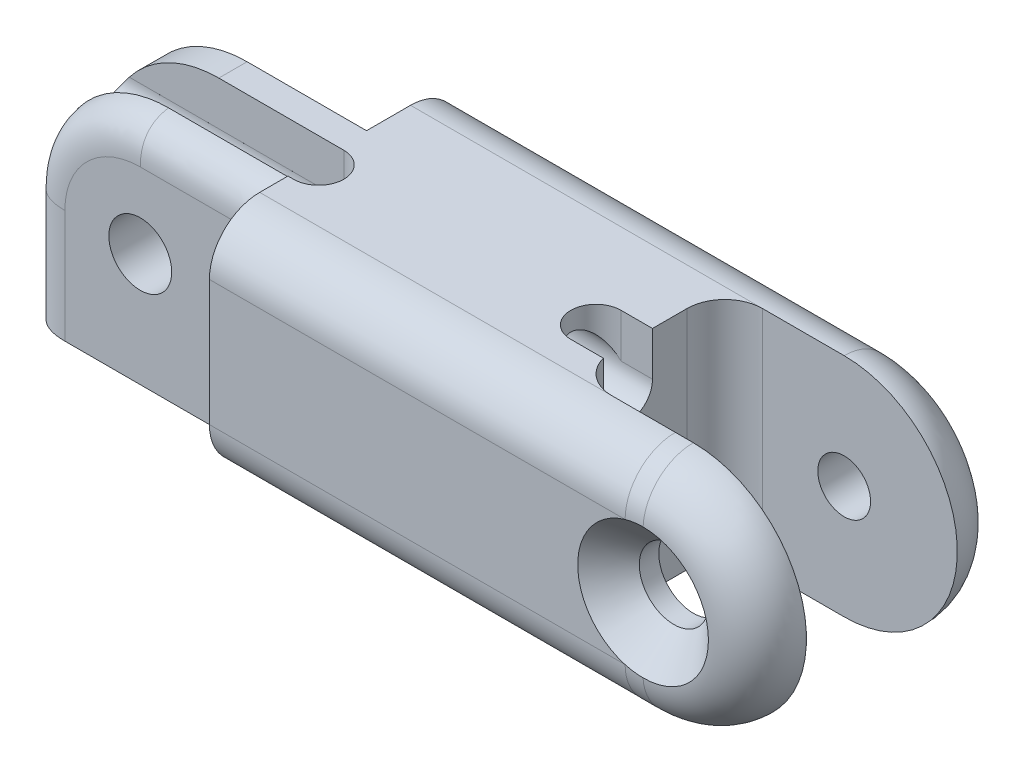
SolidWorks part; units mm, degrees
ref_plane "Front Plane" through (0, 0, 0) normal (0, 0, 1) x (1, 0, 0)
ref_plane "Top Plane" through (0, 0, 0) normal (0, 1, 0) x (1, 0, 0)
ref_plane "Right Plane" through (0, 0, 0) normal (1, 0, 0) x (0, 0, -1)
sketch "Sketch2" plane through (0, 0, 0) normal (0, 1, 0) x (1, 0, 0)
  line L0 (-12.5, 10) -> (31, 10)
  line L1 (31, 10) -> (31, 6)
  line L2 (31, 6) -> (15.5, 6)
  line L3 (12.5, 3) -> (12.5, -3)
  line L4 (15.5, -6) -> (31, -6)
  line L5 (31, -6) -> (31, -10)
  line L7 (-31, -6) -> (-31, 2.5)
  line L8 (-49.3622, 0) -> (56.3776, 0) construction
  line L9 (0, 21.2372) -> (0, -19.0689) construction
  line L10 (12.5, 3) -> (15.5, 3) construction
  line L11 (15.5, 3) -> (15.5, 6) construction
  line L16 (-12.5, -10) -> (31, -10)
  line L18 (-31, -6) -> (-12.5, -6)
  line L19 (-12.5, -6) -> (-12.5, -10)
  line L20 (-31, 2.5) -> (-12.5, 2.5)
  line L21 (-12.5, 2.5) -> (-12.5, 10)
  arc A0 (15.5, 6) -> (12.5, 3) centre (15.5, 3) ccw
  arc A1 (15.5, -6) -> (12.5, -3) centre (15.5, -3) cw
  point P13 (15.5, 3)
  dimension "D1" = 62
  dimension "D2" = 20
  dimension "D3" = 4
  dimension "D4" = 18.5
  dimension "D5" = 12
  dimension "D6" = 3
  dimension "D7" = 3
  dimension "D8" = 7.5
  dimension "D9" = 4
  dimension "D10" = 8.5
  dimension "D11" = 18.5
extrude "Boss-Extrude1" add sketch "Sketch2" along normal blind 18
sketch "Sketch5" plane through (0, 0, 10) normal (0, 0, 1) x (1, 0, 0)
  line L0 (-31, 9) -> (31.8491, 9) construction
  line L1 (-22, 18) -> (-22, 0) construction
  line L2 (31, 18) -> (31, 0) construction
  line L3 (-12.5, 18) -> (31, 18) construction
  line L4 (22, 18) -> (22, 0) construction
  line L5 (-31, 18) -> (-31, 0) construction
  line L6 (-31, 9) -> (-31, 0)
  line L7 (-31, 18) -> (-12.5, 18) construction
  line L8 (-31, 0) -> (22, 0)
  line L9 (-22, 18) -> (22, 18)
  arc A0 (-22, 18) -> (-31, 9) centre (-22, 9) ccw
  arc A1 (22, 0) -> (22, 18) centre (22, 9) ccw
  circle A2 centre (-22, 9) radius 2.5
  dimension "D2" = 5
  dimension "D1" = 9
extrude "Cut-Extrude1" cut sketch "Sketch5" against normal blind 20 flip side to cut
sketch "Sketch6" plane through (0, 0, 10) normal (0, 0, 1) x (1, 0, 0)
  line L0 (22, 0) -> (22, 18) construction
  point P4 (22, 9)
hole_wizard "CSK for M5 Countersunk Flat Head Screw1" positions "Sketch7" profile "Sketch8" countersink size "M5" standard "DIN" end condition up to next
sketch "Sketch7" plane through (0, 0, 10) normal (0, 0, 1) x (1, 0, 0)
  point P0 (22, 9)
sketch "Sketch8" plane through (22, 9, 10) normal (1, 0, 0) x (0, -1, 0)
  line L0 (0, 0) -> (0, 4)
  line L1 (0, 4) -> (2.75, 4)
  line L2 (2.75, 4) -> (2.75, 2.45)
  line L3 (2.75, 2.45) -> (5.2, 0)
  line L5 (5.2, 0) -> (0, 0)
  line L6 (-2.75, 2.45) -> (-5.2, 0) construction
  line L11 (0, -6.35) -> (0, 107.95) construction
  dimension "Thru Hole Dia." = 5.5
  dimension "Thru Hole Depth" = 4
  dimension "Near C'Sink Dia." = 10.4
  dimension "Near C'Sink Angle" = 90
hole_wizard "M5 Tapped Hole1" positions "Sketch9" profile "Sketch11" tap size "M5" standard "DIN" end condition through all
sketch "Sketch9" plane through (0, 0, 10) normal (0, 0, 1) x (1, 0, 0)
  point P0 (22, 9)
sketch "Sketch11" plane through (22, 9, 10) normal (1, 0, 0) x (0, -1, 0)
  line L0 (0, 0) -> (0, 20)
  line L1 (0, 20) -> (2.1, 20)
  line L2 (2.1, 20) -> (2.1, 3.1)
  line L3 (2.1, 3.1) -> (5.2, 0)
  line L5 (5.2, 0) -> (0, 0)
  line L6 (-2.1, 3.1) -> (-5.2, 0) construction
  line L11 (0, -6.35) -> (0, 107.95) construction
  dimension "Thru Tap Drill Dia." = 4.2
  dimension "Thru Tap Drill Depth" = 20
  dimension "Near C'Sink Dia." = 10.4
  dimension "Near C'Sink Angle" = 90
cosmetic thread "Hole Thread1" parameters "D2"=5
fillet "Fillet1" radius 4 2 edges at (4.75, 0, 10) (4.75, 18, 10)
fillet "Fillet2" radius 4 3 edges at (4.75, 0, -10) (31, 9, -10) (4.75, 18, -10)
fillet "Fillet3" radius 3 3 edges at (-31, 4.5, 6) (-17.25, 18, 6) (-28.364, 15.364, 6) conic rho 0.5
sketch "Sketch13" plane through (12.5, 0, 0) normal (1, 0, 0) x (0, 0, -1)
  line L0 (-1.75, 21.4915) -> (-1.75, -4.5302) construction
  line L1 (-3, 18) -> (3, 18) construction
  circle A0 centre (-1.75, 14.5) radius 2
  dimension "D2" = 4
  dimension "D3" = 3.5
  dimension "D1" = 1.75
extrude "Cut-Extrude2" cut sketch "Sketch13" against normal through all both and the other way through all
sketch "Sketch14" plane through (0, 18, 0) normal (0, 1, 0) x (1, 0, 0)
  line L0 (-29.1236, 0.2504) -> (-12.0557, 0.2504)
  line L1 (-29.0557, -3.75) -> (-12.0557, -3.75)
  line L3 (-29.0557, -3.75) -> (-29.1236, 0.2504)
  arc A0 (-12.0557, -3.75) -> (-12.0557, 0.2504) centre (-12.0557, -1.7498) ccw
  spline S1 degree 3 poles (-27.5797, -3) (-27.4473, -2.8693) (-27.3242, -2.7233) (-27.1669, -2.4679) (-27.12, -2.3776) (-27.0431, -2.1872) (-27.0127, -2.0851) (-26.9764, -1.8774) (-26.9703, -1.7698) (-26.9841, -1.5572) (-27.0036, -1.4537) (-27.0944, -1.1509) (-27.1934, -0.9724) (-27.4222, -0.6565) (-27.5506, -0.5207) (-27.8219, -0.2789) (-27.9619, -0.1762) (-28.3834, 0.0849) (-28.6717, 0.1991) (-29.0706, 0.2557) (-29.2006, 0.2556) (-29.4459, 0.209) (-29.5594, 0.1634) (-29.769, 0.0188) (-29.8624, -0.0793) (-30.0226, -0.3256) (-30.0911, -0.4779) (-30.1703, -0.7331) (-30.1932, -0.8231) (-30.2322, -1.0133) (-30.2481, -1.1133) (-30.2724, -1.3157) (-30.281, -1.419) (-30.2912, -1.6301) (-30.2926, -1.7379) (-30.2863, -2.055) (-30.2677, -2.2665) (-30.2021, -2.6575) (-30.1546, -2.8399) (-30.0922, -3) knots 0 0 0 0 0.0625 0.0625 0.09375 0.09375 0.125 0.125 0.15625 0.15625 0.1875 0.1875 0.25 0.25 0.3125 0.3125 0.375 0.375 0.5 0.5 0.5625 0.5625 0.625 0.625 0.6875 0.6875 0.75 0.75 0.78125 0.78125 0.8125 0.8125 0.84375 0.84375 0.875 0.875 0.9375 0.9375 1 1 1 1 construction
  spline S2 degree 3 poles (-30.0922, -3) (-30.0381, -3.1387) (-29.9701, -3.2552) (-29.8108, -3.4526) (-29.7195, -3.5323) (-29.5254, -3.6532) (-29.4205, -3.6957) (-29.205, -3.7461) (-29.094, -3.7546) (-28.7507, -3.7337) (-28.5173, -3.6588) (-28.0422, -3.4019) (-27.8092, -3.2263) (-27.5797, -3) knots 0 0 0 0 0.125 0.125 0.25 0.25 0.375 0.375 0.5 0.5 0.75 0.75 1 1 1 1 construction
  dimension "D2" = 2.0002
  dimension "D1" = 17
extrude "Cut-Extrude3" cut sketch "Sketch14" against normal blind 3.5
sketch "Sketch15" plane through (0, 18, 0) normal (0, 1, 0) x (1, 0, 0)
sketch "Sketch16" plane through (0, 18, 0) normal (0, 1, 0) x (1, 0, 0)
  line L0 (-8.0769, -1.75) -> (29.6251, -1.75) construction
  line L1 (10, 0.25) -> (19.0559, 0.25)
  line L3 (10, -3.75) -> (19.0559, -3.75)
  line L4 (19.0559, 0.25) -> (19.0559, -3.75)
  line L5 (12.5, -3) -> (12.5, 3) construction
  arc A0 (10, 0.25) -> (10, -3.75) centre (10, -1.75) ccw
  dimension "D2" = 4
  dimension "D1" = 1.75
  dimension "D3" = 2.5
extrude "Cut-Extrude4" cut sketch "Sketch16" against normal blind 3.5
